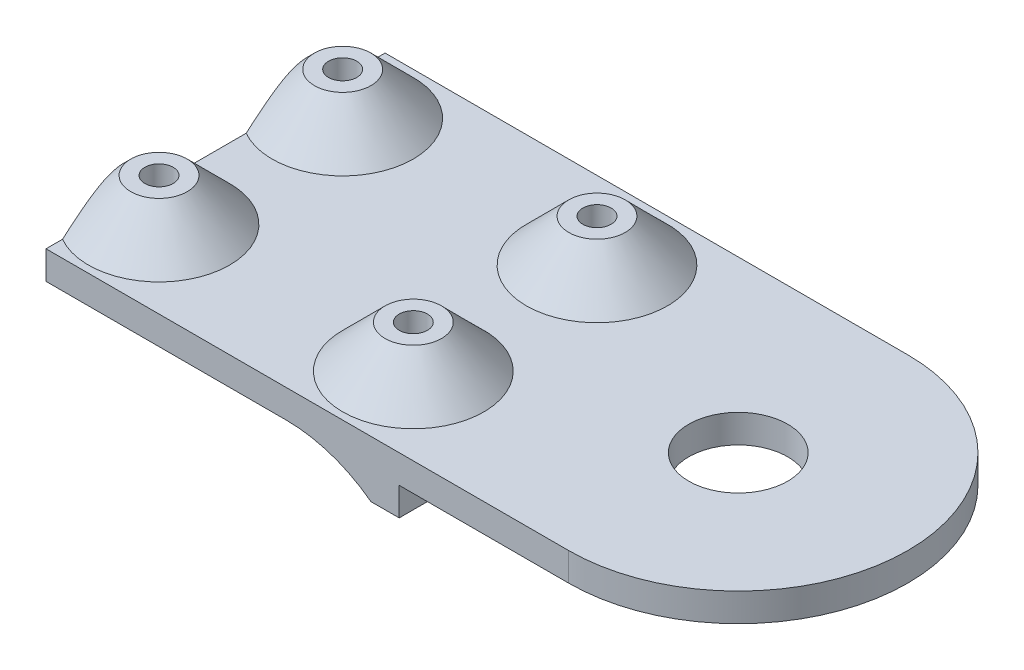
SolidWorks part; units mm, degrees
ref_plane "Plano frontal" through (0, 0, 0) normal (0, 0, 1) x (1, 0, 0)
ref_plane "Plano superior" through (0, 0, 0) normal (0, 1, 0) x (1, 0, 0)
ref_plane "Plano direito" through (0, 0, 0) normal (1, 0, 0) x (0, 0, -1)
sketch "Esboço1" plane through (0, 0, 0) normal (0, 1, 0) x (1, 0, 0)
  line L0 (11.5, 29) -> (11.5, 0) construction
  line L1 (0, 0) -> (23, 0)
  line L2 (0, 0) -> (0, 29)
  line L3 (0, 29) -> (23, 29)
  line L4 (23, 0) -> (23, 29)
  line L5 (0, 24) -> (23, 24)
  line L7 (23, 24) -> (37, 24)
  line L8 (23, 24) -> (23, 0)
  line L9 (23, 0) -> (37, 0)
  line L11 (23, 24) -> (25, 24)
  line L12 (23, 24) -> (23, 0)
  line L13 (23, 0) -> (25, 0)
  line L14 (25, 24) -> (25, 0)
  circle A0 centre (2.5, 5.5) radius 2
  circle A1 centre (2.5, 18.5) radius 2
  circle A2 centre (20.5, 5.5) radius 2
  circle A3 centre (20.5, 18.5) radius 2
  circle A4 centre (2.5, 5.5) radius 1
  circle A5 centre (2.5, 18.5) radius 1
  circle A6 centre (20.5, 5.5) radius 1
  circle A7 centre (20.5, 18.5) radius 1
  circle A8 centre (37, 12) radius 3.5
  arc A9 (37, 0) -> (37, 24) centre (37, 12) ccw
  dimension "D3" = 4
  dimension "D7" = 4
  dimension "D10" = 2
  dimension "D11" = 2
  dimension "D14" = 7
  dimension "D12" = 12
  dimension "D15" = 12
  dimension "D1" = 29
  dimension "D2" = 23
  dimension "D4" = 5.5
  dimension "D5" = 2.5
  dimension "D6" = 2.5
  dimension "D8" = 13
  dimension "D9" = 5.5
  dimension "D13" = 2
extrude "Ressalto-extrusão1" add sketch "Esboço1" along normal blind 2 contours L0 L5 L2 L1 A1 A0 | L5 L0 L1 L4 A3 A2 | L9 A9 L7 L14 A8 | L14 L7 L4 L9 region at (16.9244, 0, -12) region at (6.0756, 0, -12) region at (24, 0, -12) region at (31, 0, -23.6606)
extrude "Ressalto-extrusão2" add sketch "Esboço1<3>" along normal blind 5 contours A3 A7 | A1 A5 | A0 A4 | A2 A6 region at (0.5566, 0, -5.5) region at (0.5566, 0, -18.5) region at (18.5566, 0, -5.5) region at (18.5566, 0, -18.5)
sketch "Esboço1<3>" plane through (0, 0, 0) normal (0, 1, 0) x (1, 0, 0) same geometry as "Esboço1"
extrude "Ressalto-extrusão3" add sketch "Esboço1<4>" against normal blind 2 contours L14 L7 L4 L9 region at (24, 0, -12)
sketch "Esboço1<4>" plane through (0, 0, 0) normal (0, 1, 0) x (1, 0, 0) same geometry as "Esboço1"
chamfer "Chanfro1" distance 3 angle 45 4 edges at (20.5, 2, -3.5) (20.5, 2, -16.5) (2.5, 2, -3.5) (2.5, 2, -16.5)
fillet "Filete1" radius 10 1 edges at (23, 0, -12)
